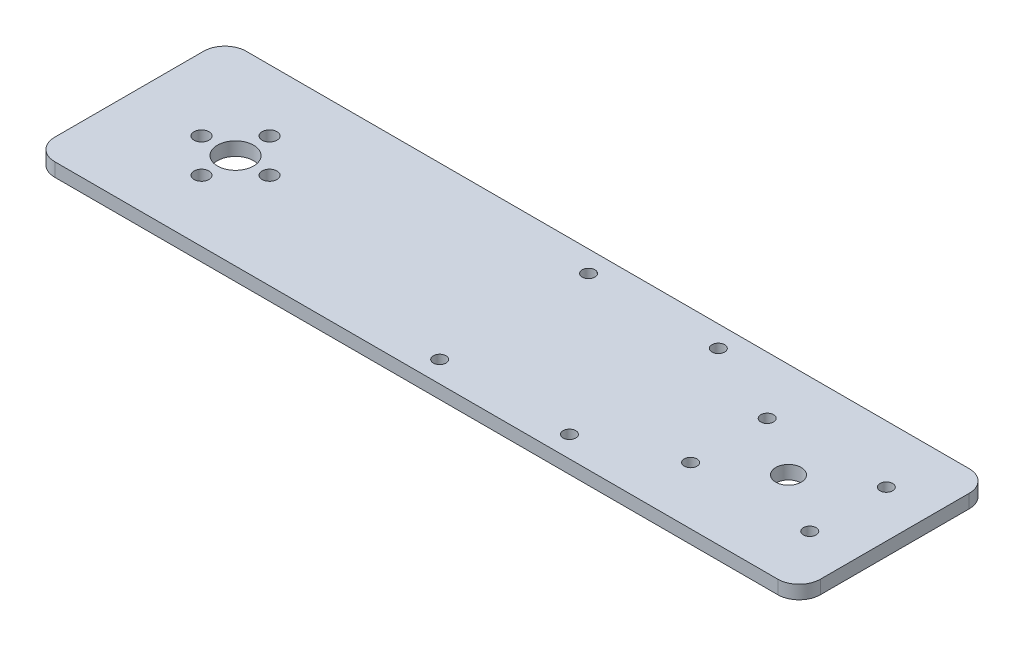
SolidWorks part; units mm, degrees
ref_plane "Front Plane" through (0, 0, 0) normal (0, 0, 1) x (1, 0, 0)
ref_plane "Top Plane" through (0, 0, 0) normal (0, 1, 0) x (1, 0, 0)
ref_plane "Right Plane" through (0, 0, 0) normal (1, 0, 0) x (0, 0, -1)
sketch "Sketch1" plane through (0, 0, 0) normal (0, 1, 0) x (1, 0, 0)
  line L1 (-25, 22.5) -> (155, 22.5)
  line L2 (-25, 22.5) -> (-25, -22.5)
  line L3 (-25, -22.5) -> (155, -22.5)
  line L4 (155, 22.5) -> (155, -22.5)
  point P4 (-25, 0)
  dimension "D1" = 45
  dimension "D2" = 180
  dimension "D3" = 25
extrude "Boss-Extrude1" add sketch "Sketch1" along normal blind 3.175
fillet "Fillet1" radius 5 4 edges at (-25, 1.5875, 22.5) (-25, 1.5875, -22.5) (155, 1.5875, -22.5) (155, 1.5875, 22.5)
sketch "Sketch4" plane through (0, 3.175, 0) normal (0, 1, 0) x (1, 0, 0)
  line L0 (155, 0) -> (-25, 0) construction
  line L1 (155, -17.5) -> (155, 17.5) construction
  line L2 (-25, 17.5) -> (-25, -17.5) construction
  line L3 (130, 22.5) -> (130, -22.5) construction
  line L4 (150, 22.5) -> (-20, 22.5) construction
  line L5 (-20, -22.5) -> (150, -22.5) construction
  circle A0 centre (130, 0) radius 3
  circle A1 centre (116, 9) radius 1.5
  circle A2 centre (144, 9) radius 1.5
  circle A3 centre (144, -9) radius 1.5
  circle A4 centre (116, -9) radius 1.5
  dimension "D1" = 6
  dimension "D5" = 3
  dimension "D2" = 25
  dimension "D3" = 14
  dimension "D4" = 9
extrude "Cut-Extrude1" cut sketch "Sketch4" against normal through all
sketch "Sketch5" plane through (0, 3.175, 0) normal (0, 1, 0) x (1, 0, 0)
  circle A0 centre (0, 0) radius 4.25
  dimension "D1" = 8.5
extrude "Cut-Extrude2" cut sketch "Sketch5" against normal through all
sketch "Sketch10" plane through (0, 3.175, 0) normal (0, 1, 0) x (1, 0, 0)
  line L0 (-25, 0) -> (155, 0) construction
  line L1 (-25, 17.5) -> (-25, -17.5) construction
  line L2 (155, -17.5) -> (155, 17.5) construction
  line L3 (-20, -22.5) -> (150, -22.5) construction
  circle A0 centre (65.5, -17.5) radius 1.5
  circle A2 centre (96, -17.5) radius 1.5
  circle A3 centre (116, -9) radius 1.5 construction
  circle A4 centre (96, 17.5) radius 1.5
  circle A5 centre (65.5, 17.5) radius 1.5
  dimension "D3" = 3
  dimension "D4" = 20
  dimension "D1" = 30.5
  dimension "D2" = 5
extrude "Cut-Extrude4" cut sketch "Sketch10" against normal through all
sketch "Sketch11" plane through (0, 3.175, 0) normal (0, 1, 0) x (1, 0, 0)
  line L0 (-25, 17.5) -> (-25, -17.5) construction
  circle A0 centre (8, 0) radius 1.75
  circle A1 centre (0, 0) radius 4.25 construction
  circle A2 centre (0, -8) radius 1.75
  circle A3 centre (-8, 0) radius 1.75
  circle A4 centre (0, 8) radius 1.75
  point P4 (0, 0)
  point P7 (-25, 0)
  point P8 (-8.3857, 0)
  dimension "D1" = 3.5
  dimension "D2" = 8
  dimension "D3" = 16
extrude "Cut-Extrude5" cut sketch "Sketch11" against normal through all
